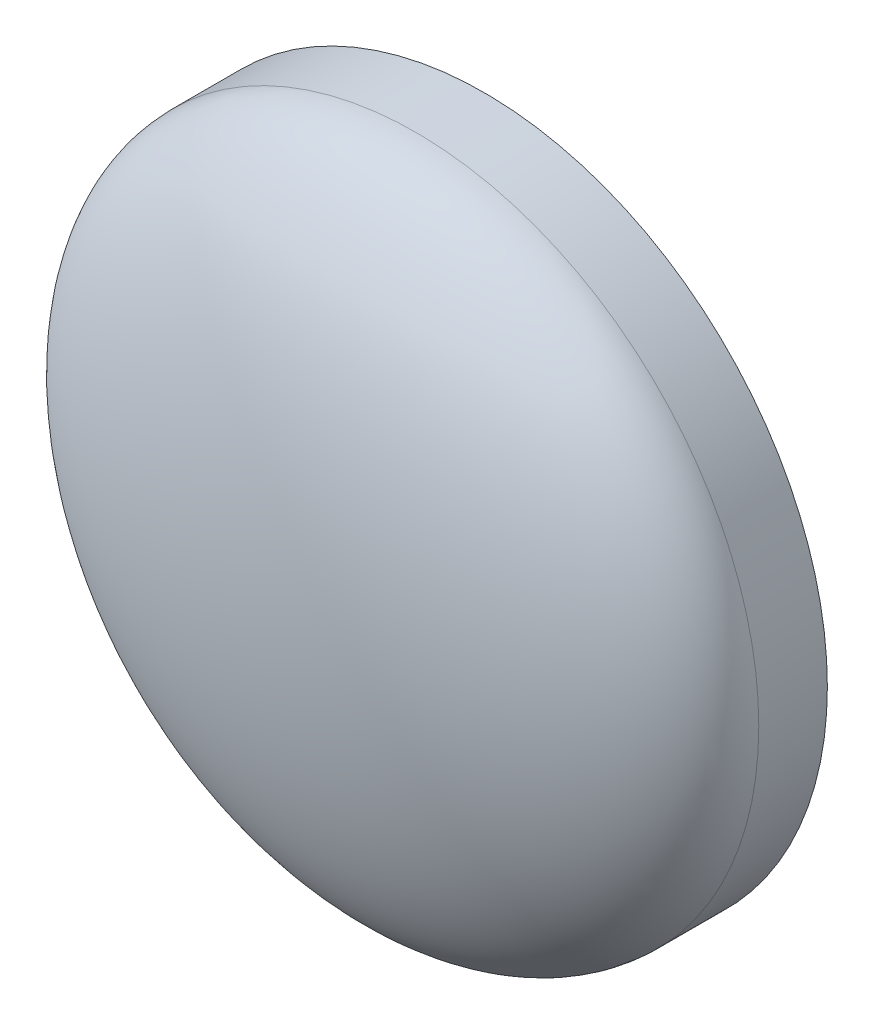
SolidWorks part; units mm, degrees
material "Chêne"
ref_plane "Plan de face" through (0, 0, 0) normal (0, 0, 1) x (1, 0, 0)
ref_plane "Plan de dessus" through (0, 0, 0) normal (0, 1, 0) x (1, 0, 0)
ref_plane "Plan de droite" through (0, 0, 0) normal (1, 0, 0) x (0, 0, -1)
sketch "Esquisse1" plane through (0, 0, 0) normal (0, 0, 1) x (1, 0, 0)
  line L3 (13.9264, -3.8067) -> (12.9737, -3.3729)
  line L4 (12.0096, -8.0124) -> (11.0568, -7.5785)
  arc A0 (12.2086, -8.7589) -> (14.6201, -3.467) centre (0, 0) cw
  arc A1 (12.0096, -8.0124) -> (12.2086, -8.7589) centre (11.8024, -8.4674) cw
  arc A2 (12.6927, -2.8098) -> (12.9737, -3.3729) centre (13.1809, -2.9178) ccw
  arc A3 (13.9264, -3.8067) -> (14.6201, -3.467) centre (14.1336, -3.3517) ccw
  arc A4 (12.6927, -2.8098) -> (10.4477, -7.736) centre (0, 0) ccw
  arc A5 (10.4477, -7.736) -> (11.0568, -7.5785) centre (10.8496, -8.0335) cw
  circle A6 centre (0, 0) radius 25
  point P116 (0, 0)
  point P374 (0, 0)
extrude "Boss.-Extru.1" add sketch "Esquisse1" along normal blind 5 contours A6
extrude "Enlèv. mat.-Extru.1" cut sketch "Esquisse1<7>" along normal blind 3 contours A0 A3 L3 A2 A4 A5 L4 A1
sketch "Esquisse1<7>" plane through (0, 0, 0) normal (0, 0, 1) x (1, 0, 0) same geometry as "Esquisse1"
dome "Dôme1" faces to dome 1 distance 10 reverse direction no elliptical dome yes face at (25, 0, 5) parameters "D1"=10
